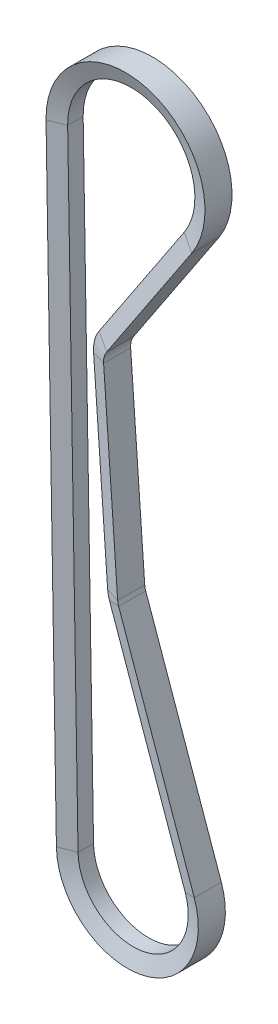
SolidWorks part; units mm, degrees
ref_plane "Front Plane" through (0, 0, 0) normal (0, 0, 1) x (1, 0, 0)
ref_plane "Top Plane" through (0, 0, 0) normal (0, 1, 0) x (1, 0, 0)
ref_plane "Right Plane" through (0, 0, 0) normal (1, 0, 0) x (0, 0, -1)
sketch "Sketch2" plane through (0, 0, 0) normal (0, 0, 1) x (1, 0, 0)
  line L0 (0, 0) -> (1, 0) construction
  line L1 (0, 0) -> (0, 1) construction
  line L12 (-24.9966, -0.4153) -> (-28.6509, 219.5339)
  line L14 (22.67, 204.5086) -> (-7.3229, 159.3467)
  line L15 (-8.3672, 155.3843) -> (-3.4135, 85.5598)
  line L16 (-3.0682, 83.898) -> (23.5778, 8.3118)
  arc A4 (-28.6509, 219.5339) -> (22.67, 204.5086) centre (-0.6548, 219.999) cw
  arc A7 (23.5778, 8.3118) -> (-24.9966, -0.4153) centre (0, 0) cw
  arc A8 (-7.3229, 159.3467) -> (-8.3672, 155.3843) centre (-2.0332, 155.8336) ccw
  arc A9 (-3.4135, 85.5598) -> (-3.0682, 83.898) centre (2.9206, 86.0091) ccw
ref_plane "Plane4" through (23.5778, 8.3118, 0) normal (0.3325, -0.9431, 0) x (-0.9431, -0.3325, 0)
sketch "Sketch3" plane through (23.5778, 8.3118, 0) normal (0.3325, -0.9431, 0) x (-0.9431, -0.3325, 0)
  line L0 (0, -4.7625) -> (0, 4.7625)
  line L1 (0, -4.7625) -> (5.588, -2.7286)
  line L2 (5.588, -2.7286) -> (5.588, 2.7286)
  line L3 (5.588, 2.7286) -> (0, 4.7625)
  line L4 (0, 0) -> (5.588, 0) construction
  dimension "D1" = 9.525
  dimension "D2" = 5.588
  dimension "D3" = 40
sweep "Sweep1" add profiles "Sketch3" path "Sketch2"
